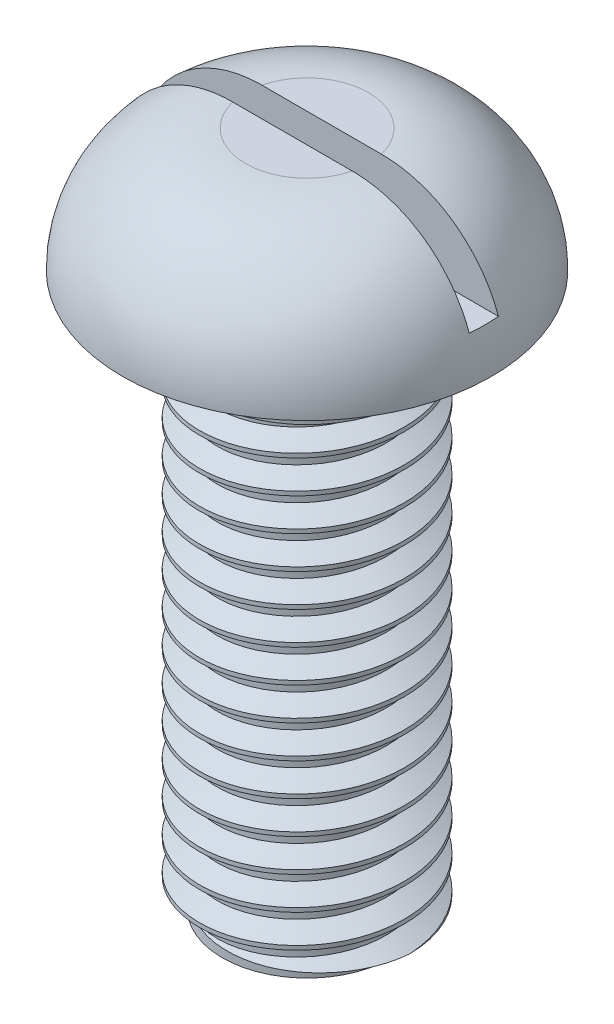
SolidWorks part; units mm, degrees
ref_plane "Спереди" through (0, 0, 0) normal (0, 0, 1) x (1, 0, 0)
ref_plane "Сверху" through (0, 0, 0) normal (0, 1, 0) x (1, 0, 0)
ref_plane "Справа" through (0, 0, 0) normal (1, 0, 0) x (0, 0, -1)
sketch "Эскиз1" plane through (0, 0, 0) normal (0, 1, 0) x (1, 0, 0)
  circle A0 centre (0, 0) radius 2.5
  dimension "D1" = 5
extrude "Бобышка-Вытянуть2" add sketch "Эскиз1" along normal blind 14
sketch "Эскиз3" plane through (0, 14, 0) normal (0, 1, 0) x (1, 0, 0)
  circle A0 centre (0, 0) radius 4.5
  dimension "D1" = 9
extrude "Бобышка-Вытянуть3" add sketch "Эскиз3" along normal blind 3
fillet "Скругление3" radius 3 1 edges at (0, 17, 4.5)
sketch "Эскиз4" plane through (0, 17, 0) normal (0, 1, 0) x (1, 0, 0)
  line L1 (-5.6666, -0.3561) -> (5.6666, -0.3561)
  line L2 (-5.6666, -0.3561) -> (-5.6666, 0.3561)
  line L3 (-5.6666, 0.3561) -> (5.6666, 0.3561)
  line L4 (5.6666, -0.3561) -> (5.6666, 0.3561)
  line L5 (-5.6666, -0.3561) -> (5.6666, 0.3561) construction
  line L6 (-5.6666, 0.3561) -> (5.6666, -0.3561) construction
  point P0 (0, 0)
extrude "Вырез-Вытянуть1" cut sketch "Эскиз4" against normal blind 2
thread "Резьба1" pitch 0.8 method cut profile "Профиль резьбы1" start angle 0, offset 0, length 13, pitch 0.8, diameter 5
ref_plane "Плоскость4" through (2.5, 0, 0) normal (0, 0, 1) x (1, 0, 0)
sketch "Профиль резьбы1" plane through (2.5, 0, 0) normal (0, 0, 1) x (1, 0, 0)
  line L0 (0, 0) -> (0, 0.8) construction
  line L11 (0, 0) -> (0, 0.7)
  line L12 (0, 0.7) -> (-0.433, 0.45)
  line L13 (-0.433, 0.45) -> (-0.433, 0.25)
  line L15 (-0.433, 0.25) -> (0, 0)
  line L17 (-0.433, 0.35) -> (0, 0.35) construction
  point P2 (0, 0)
  dimension "Pitch" = 0.8
  dimension "Profile_Angle" = 60
  dimension "Profile_Land" = 0.2
  dimension "Profile_Height" = 0.433
sketch "Эскиз11" plane through (0, 0, 0) normal (0, -1, 0) x (-1, 0, 0)
  circle A0 centre (0, 0) radius 2.5
extrude "Вырез-Вытянуть2" cut sketch "Эскиз11" against normal blind 0.5
sketch "Эскиз12" plane through (0, 0.5, 0) normal (0, -1, 0) x (1, 0, 0)
  circle A0 centre (0, 0) radius 2.5
extrude "Бобышка-Вытянуть5" add sketch "Эскиз12" along normal blind 2 from offset 14 offset against normal yes
sketch "Эскиз13" plane through (0, 0.5, 0) normal (0, -1, 0) x (-1, 0, 0)
  circle A0 centre (0, 0) radius 2.067
  circle A1 centre (0, 0) radius 3.0219
extrude "Вырез-Вытянуть3" cut sketch "Эскиз13" against normal blind 0.3
